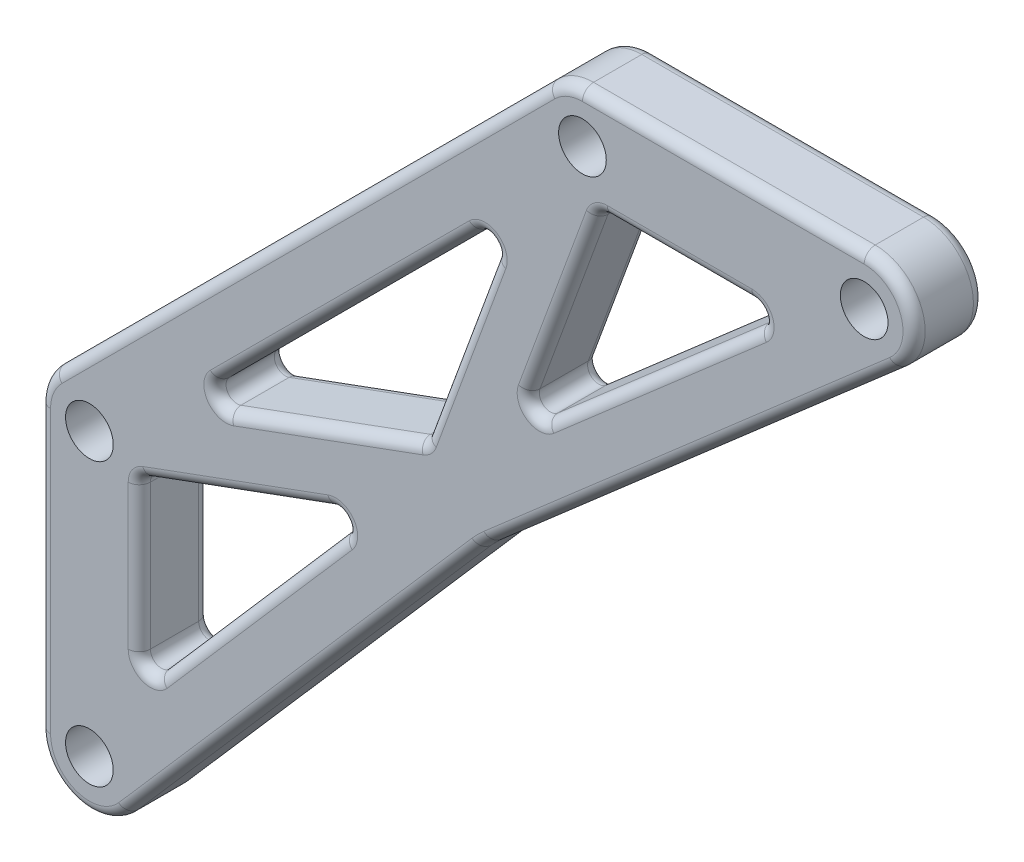
SolidWorks part; units mm, degrees
ref_plane "Front Plane" through (0, 0, 0) normal (0, 0, 1) x (1, 0, 0)
ref_plane "Top Plane" through (0, 0, 0) normal (0, 1, 0) x (1, 0, 0)
ref_plane "Right Plane" through (0, 0, 0) normal (1, 0, 0) x (0, 0, -1)
sketch "Sketch1" plane through (0, 0, 0) normal (0, 0, 1) x (1, 0, 0)
  line L0 (0, 0) -> (0, 25.4) construction
  line L1 (0, 25.4) -> (44.45, 69.85) construction
  line L2 (44.45, 69.85) -> (69.85, 69.85) construction
  line L3 (0, 25.4) -> (32.5134, 37.3366) construction
  line L4 (32.5134, 37.3366) -> (44.45, 69.85) construction
  line L5 (32.5134, 37.3366) -> (69.85, 69.85) construction
  line L6 (0, 0) -> (32.5134, 37.3366) construction
  line L7 (4.5, 23.8563) -> (4.5, 7.4516)
  line L8 (4.5, 7.4516) -> (25.4989, 31.5656)
  line L9 (25.4989, 31.5656) -> (4.5, 23.8563)
  line L10 (8.4016, 31.6802) -> (30.1758, 39.6742)
  line L11 (30.1758, 39.6742) -> (38.1698, 61.4484)
  line L12 (38.1698, 61.4484) -> (8.4016, 31.6802)
  line L13 (45.9937, 65.35) -> (38.2844, 44.3511)
  line L14 (38.2844, 44.3511) -> (62.3984, 65.35)
  line L15 (62.3984, 65.35) -> (45.9937, 65.35)
  line L16 (-4.5, 25.4) -> (-4.5, 0)
  line L17 (3.3936, -2.9552) -> (35.703, 34.147)
  line L18 (72.8052, 66.4564) -> (35.703, 34.147)
  line L19 (32.5134, 37.3366) -> (35.703, 34.147) construction
  line L20 (-3.182, 28.582) -> (41.268, 73.032)
  line L21 (44.45, 74.35) -> (69.85, 74.35)
  circle A0 centre (0, 0) radius 2.15
  circle A1 centre (0, 25.4) radius 2.15
  circle A2 centre (44.45, 69.85) radius 2.15
  circle A3 centre (69.85, 69.85) radius 2.15
  circle A6 centre (0, 25.4) radius 4.5
  circle A7 centre (44.45, 69.85) radius 4.5
  circle A8 centre (69.85, 69.85) radius 4.5
  circle A9 centre (0, 0) radius 4.5
  point P9 (19.043, 50.807)
  dimension "D5" = 4.3
  dimension "D7" = 9
  dimension "D1" = 25.4
  dimension "D2" = 25.4
  dimension "D3" = 44.45
  dimension "D4" = 44.45
  dimension "D6" = 19.05
  dimension "D8" = 9
  dimension "D9" = 6
  dimension "D10" = 6
  dimension "D11" = 6
  dimension "D12" = 6
  dimension "D13" = 6
  dimension "D14" = 9
  dimension "D15" = 6
  dimension "D16" = 6
extrude "Boss-Extrude1" add sketch "Sketch1" along normal blind 6.35 contours A9 L17 L18 A8 L21 A7 L20 A6 L16 L15 L14 L13 L12 L11 L10 L9 L8 L7 | A9 A0 | A6 A1 | A7 A2 | A8 A3 region at (0, 19.8067, 0) region at (-4.0399, 27.0734, 0) region at (0, 4.3727, 0) region at (42.7766, 73.8899, 0) region at (65.7549, 68.3169, 0)
fillet "Fillet1" radius 1 9 edges at (62.3984, 65.35, 3.175) (38.2844, 44.3511, 3.175) (45.9937, 65.35, 3.175) (30.1758, 39.6742, 3.175) (38.1698, 61.4484, 3.175) (8.4016, 31.6802, 3.175) (25.4989, 31.5656, 3.175) (4.5, 7.4516, 3.175) (4.5, 23.8563, 3.175)
fillet "Fillet2" radius 10 1 edges at (35.703, 34.147, 3.175)
fillet "Fillet3" radius 1 56 edges at (23.0097, 29.8513, 0) (14.5972, 19.0467, 0) (5.1494, 9.1862, 0) (4.5, 16.6404, 0) (4.68, 23.7306, 0) (30.1037, 39.7463, 0) (21.2026, 36.3799, 0) (11.4767, 33.6454, 0) (23.2857, 46.5643, 0) (36.2046, 58.3733, 0) (39.9987, 46.8403, 0) (42.6901, 56.3516, 0) (46.1194, 65.17, 0) (53.2096, 65.35, 0) (60.6638, 64.7006, 0) (74.0643, 71.4278, 0) (57.15, 74.35, 0) (42.7279, 74.0075, 0) (19.043, 50.807, 0) (-4.1575, 27.1221, 0) (-4.5, 12.7, 0) (-1.5778, -4.2143, 0) (19.3216, 15.3355, 0) (35.7198, 34.1302, 0) (23.0097, 29.8513, 6.35) (14.5972, 19.0467, 6.35) (5.1494, 9.1862, 6.35) (4.5, 16.6404, 6.35) (4.68, 23.7306, 6.35) (46.1194, 65.17, 6.35) (53.2096, 65.35, 6.35) (60.6638, 64.7006, 6.35) (50.8033, 55.2528, 6.35) (39.9987, 46.8403, 6.35) (36.2046, 58.3733, 6.35) (33.4701, 48.6474, 6.35) (30.1037, 39.7463, 6.35) (21.2026, 36.3799, 6.35) (11.4767, 33.6454, 6.35) (-4.1575, 27.1221, 6.35) (-4.5, 12.7, 6.35) (-1.5778, -4.2143, 6.35) (19.3216, 15.3355, 6.35) (35.7198, 34.1302, 6.35) (54.5145, 50.5284, 6.35) (74.0643, 71.4278, 6.35) (57.15, 74.35, 6.35) (42.7279, 74.0075, 6.35) (13.4984, 27.1599, 0) (33.4701, 48.6474, 0) (50.8033, 55.2528, 0) (54.5145, 50.5284, 0) (13.4984, 27.1599, 6.35) (42.6901, 56.3516, 6.35) (23.2857, 46.5643, 6.35) (19.043, 50.807, 6.35)
